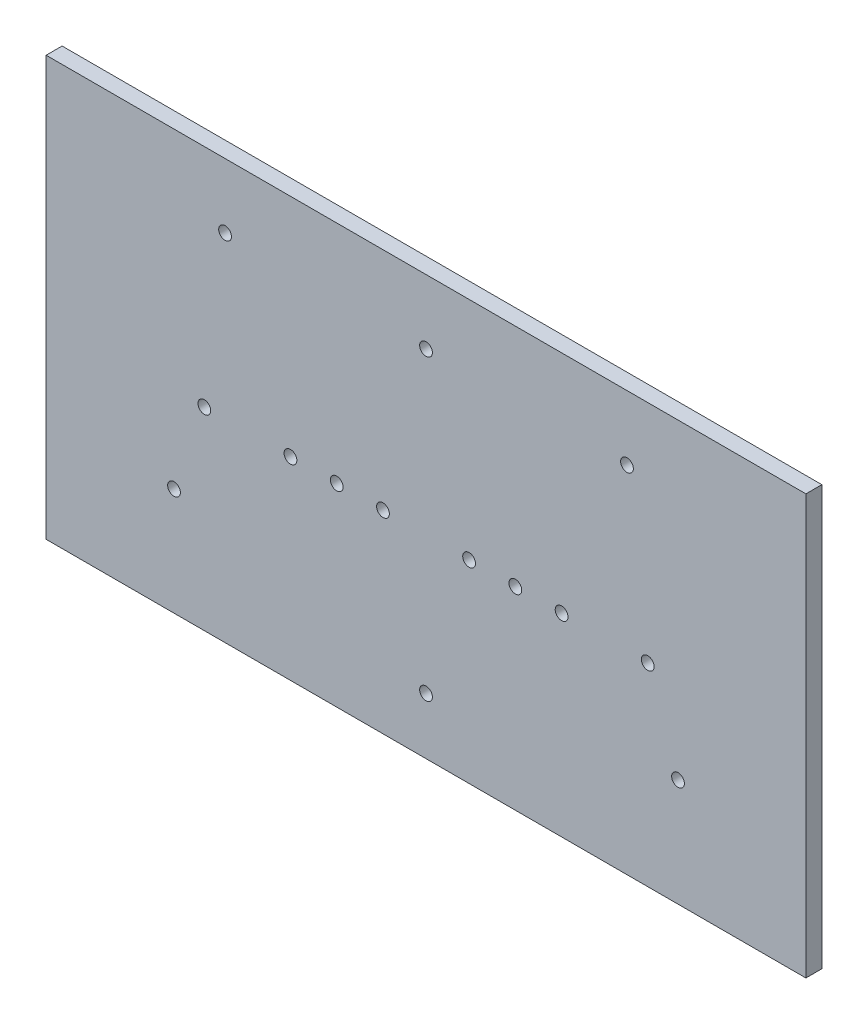
SolidWorks part; units mm, degrees
ref_plane "前视基准面" through (0, 0, 0) normal (0, 0, 1) x (1, 0, 0)
ref_plane "上视基准面" through (0, 0, 0) normal (0, 1, 0) x (1, 0, 0)
ref_plane "右视基准面" through (0, 0, 0) normal (1, 0, 0) x (0, 0, -1)
sketch "草图1" plane through (0, 0, 0) normal (0, 0, 1) x (-1, 0, 0)
  line L16 (66, 53) -> (-66, 53)
  line L17 (-66, 53) -> (-87, 32)
  line L18 (-87, 32) -> (-87, -32)
  line L19 (-87, -32) -> (-66, -53)
  line L20 (-66, -53) -> (66, -53)
  line L21 (66, -53) -> (87, -32)
  line L22 (87, -32) -> (87, 32)
  line L23 (87, 32) -> (66, 53)
  circle A2 centre (0, -45.5) radius 2
  circle A4 centre (28, 5) radius 2
  circle A6 centre (13.5, 5) radius 2
  circle A8 centre (-13.5, 5) radius 2
  circle A10 centre (-28, 5) radius 2
  circle A12 centre (-42.5, 5) radius 2
  circle A14 centre (-69.5, 5) radius 2
  circle A16 centre (-63, -45.5) radius 2
  circle A18 centre (63, -45.5) radius 2
  circle A20 centre (42.5, 5) radius 2
  circle A22 centre (69.5, 5) radius 2
  circle A24 centre (79, 32) radius 2
  circle A26 centre (-79, 32) radius 2
  circle A28 centre (0, 48) radius 2
sketch "草图2" plane through (0, 0, 0) normal (0, 0, 1) x (1, 0, 0)
  line L0 (69, -57) -> (-69, -57)
  line L1 (69, 55) -> (-69, 55)
  line L2 (89, 35) -> (89, -35)
  line L3 (69, -55) -> (-69, -55)
  line L4 (-89, 35) -> (-89, -35)
  line L5 (89, 55) -> (-89, -55) construction
  line L6 (89, -55) -> (-89, 55) construction
  line L7 (-91, 35) -> (-91, -35)
  line L8 (-66, -53) -> (66, -53)
  line L9 (66, -53) -> (87, -32)
  line L10 (87, -32) -> (87, 32)
  line L11 (87, 32) -> (66, 53)
  line L12 (66, 53) -> (-66, 53)
  line L13 (-66, 53) -> (-87, 32)
  line L14 (-87, 32) -> (-87, -32)
  line L15 (-87, -32) -> (-66, -53)
  line L16 (-66, -53) -> (66, -53)
  line L17 (66, -53) -> (87, -32)
  line L18 (87, -32) -> (87, 32)
  line L19 (87, 32) -> (66, 53)
  line L20 (66, 53) -> (-66, 53)
  line L21 (-66, 53) -> (-87, 32)
  line L22 (-87, 32) -> (-87, -32)
  line L23 (-87, -32) -> (-66, -53)
  line L24 (69, 57) -> (-69, 57)
  line L25 (91, 35) -> (91, -35)
  line L27 (119.0896, 65.7214) -> (-119.0896, 65.7214)
  line L28 (119.0896, 65.7214) -> (119.0896, -65.7214)
  line L29 (119.0896, -65.7214) -> (-119.0896, -65.7214)
  line L30 (-119.0896, 65.7214) -> (-119.0896, -65.7214)
  line L31 (119.0896, 65.7214) -> (-119.0896, -65.7214) construction
  line L32 (119.0896, -65.7214) -> (-119.0896, 65.7214) construction
  arc A0 (89, -35) -> (69, -55) centre (69, -35) cw
  circle A1 centre (-28, -5) radius 2
  circle A2 centre (-28, -5) radius 2
  circle A3 centre (0, 45.5) radius 2
  circle A4 centre (0, 45.5) radius 2
  circle A5 centre (69.5, -5) radius 2
  circle A6 centre (69.5, -5) radius 2
  circle A7 centre (42.5, -5) radius 2
  circle A8 centre (42.5, -5) radius 2
  circle A9 centre (28, -5) radius 2
  circle A10 centre (28, -5) radius 2
  circle A11 centre (13.5, -5) radius 2
  circle A12 centre (13.5, -5) radius 2
  circle A13 centre (-13.5, -5) radius 2
  circle A14 centre (-13.5, -5) radius 2
  circle A15 centre (-79, -32) radius 2
  circle A16 centre (-79, -32) radius 2
  circle A17 centre (-69.5, -5) radius 2
  circle A18 centre (-69.5, -5) radius 2
  circle A19 centre (-42.5, -5) radius 2
  circle A20 centre (-42.5, -5) radius 2
  circle A21 centre (-63, 45.5) radius 2
  circle A22 centre (-63, 45.5) radius 2
  circle A23 centre (63, 45.5) radius 2
  circle A24 centre (63, 45.5) radius 2
  circle A25 centre (0, -48) radius 2
  circle A26 centre (0, -48) radius 2
  circle A27 centre (79, -32) radius 2
  circle A28 centre (79, -32) radius 2
  arc A29 (-69, -55) -> (-89, -35) centre (-69, -35) cw
  arc A30 (-69, 55) -> (-89, 35) centre (-69, 35) ccw
  arc A31 (69, 55) -> (89, 35) centre (69, 35) cw
  arc A32 (91, -35) -> (69, -57) centre (69, -35) cw
  arc A33 (-69, -57) -> (-91, -35) centre (-69, -35) cw
  arc A34 (-69, 57) -> (-91, 35) centre (-69, 35) ccw
  arc A35 (69, 57) -> (91, 35) centre (69, 35) cw
  point P8 (0, 0)
  point P80 (0, 0)
  point P85 (-119.0896, -65.7214)
  dimension "D18" = 20
  dimension "D16" = 2
  dimension "D17" = 2
  dimension "D19" = 2
  dimension "D1" = 0
  dimension "D2" = 0
  dimension "D3" = 0
  dimension "D4" = 0
  dimension "D5" = 0
  dimension "D6" = 0
  dimension "D7" = 0
  dimension "D8" = 0
  dimension "D9" = 0
  dimension "D10" = 0
  dimension "D11" = 0
  dimension "D12" = 0
  dimension "D13" = 0
  dimension "D14" = 0
  dimension "D15" = 0
extrude "凸台-拉伸1" add sketch "草图2" along normal blind 5 contours L22 L23 L16 L17 L18 L19 L20 L21 A28 A26 A24 A22 A20 A18 A16 A14 A12 A10 A8 A6 A4 A2 | A31 L1 A30 L4 A29 L3 A0 L2 L23 L22 L21 L20 L19 L18 L17 L16 | A35 L24 A34 L7 A33 L0 A32 L25 L1 A31 L2 A0 L3 A29 L4 A30 | L27 L30 L29 L28 L24 A35 L25 A32 L0 A33 L7 A34 region at (0, -56.7852, 0) region at (81.6625, 47.6625, 0) region at (0, 0.0112, 0) region at (116.3692, 0, 0)
extrude "切除-拉伸1" cut sketch "草图2<3>" along normal blind 1 contours A35 L24 A34 L7 A33 L0 A32 L25 L1 A31 L2 A0 L3 A29 L4 A30 region at (0, -56.7852, 0)
sketch "草图2<3>" plane through (0, 0, 0) normal (0, 0, 1) x (1, 0, 0) same geometry as "草图2"
